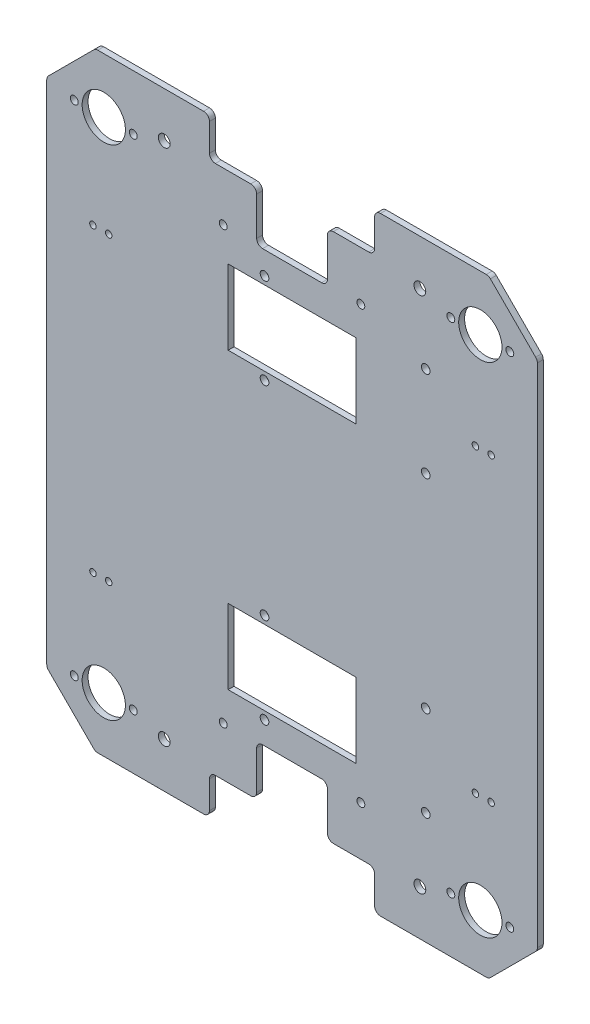
SolidWorks part; units mm, degrees
material "Alliage 1060"
ref_plane "Plan de dessus" through (0, 0, 0) normal (0, 0, 1) x (1, 0, 0)
ref_plane "Plan de droite" through (0, 0, 0) normal (0, 1, 0) x (1, 0, 0)
ref_plane "Plan de face" through (0, 0, 0) normal (1, 0, 0) x (0, 0, -1)
sketch "Esquisse1" plane through (0, 0, 0) normal (0, 0, 1) x (1, 0, 0)
  line L0 (0, 0) -> (-200, 0)
  line L1 (-200, 0) -> (-224.7487, 24.7487)
  line L2 (-224.7487, 24.7487) -> (-224.7487, 284.7487)
  line L3 (-224.7487, 284.7487) -> (-200, 309.4975)
  line L4 (-200, 309.4975) -> (0, 309.4975)
  line L5 (0, 309.4975) -> (24.7487, 284.7487)
  line L6 (24.7487, 284.7487) -> (24.7487, 24.7487)
  line L7 (24.7487, 24.7487) -> (0, 0)
  dimension "D1" = 260
  dimension "D2" = 35
  dimension "D3" = 135
  dimension "D4" = 200
extrude "Base" add sketch "Esquisse1" along normal blind 3
sketch "Esquisse3" plane through (0, 0, 0) normal (0, 0, -1) x (-1, 0, 0)
  line L0 (142, 0) -> (142, 20)
  line L1 (200, 0) -> (0, 0) construction
  line L2 (142, 20) -> (118, 20)
  line L3 (118, 20) -> (118, 45.5)
  line L4 (118, 45.5) -> (82, 45.5)
  line L5 (82, 45.5) -> (82, 20)
  line L6 (82, 20) -> (58, 20)
  line L7 (58, 20) -> (58, 0)
  line L8 (-24.7487, 154.7487) -> (224.7487, 154.7487) construction
  line L9 (-24.7487, 24.7487) -> (-24.7487, 284.7487) construction
  line L10 (224.7487, 284.7487) -> (224.7487, 24.7487) construction
  line L11 (58, 0) -> (142, 0)
  line L12 (58, 309.4975) -> (142, 309.4975)
  line L13 (142, 309.4975) -> (142, 289.4975)
  line L14 (142, 289.4975) -> (118, 289.4975)
  line L15 (118, 289.4975) -> (118, 263.9975)
  line L16 (118, 263.9975) -> (82, 263.9975)
  line L17 (82, 263.9975) -> (82, 289.4975)
  line L18 (82, 289.4975) -> (58, 289.4975)
  line L19 (58, 289.4975) -> (58, 309.4975)
  line L20 (100, 45.5) -> (100, -49954.5) construction
  line L21 (0, 309.4975) -> (200, 309.4975) construction
  line L22 (67.5, 244.4975) -> (132.5, 244.4975)
  line L23 (67.5, 244.4975) -> (67.5, 214.4975)
  line L24 (67.5, 214.4975) -> (132.5, 214.4975)
  line L25 (132.5, 244.4975) -> (132.5, 214.4975)
  line L26 (132.5, 65) -> (132.5, 95)
  line L27 (67.5, 95) -> (132.5, 95)
  line L28 (67.5, 65) -> (132.5, 65)
  line L29 (67.5, 65) -> (67.5, 95)
  circle A0 centre (65, 45) radius 2
  circle A1 centre (135, 45) radius 2
  circle A2 centre (135, 264.4975) radius 2
  circle A3 centre (65, 264.4975) radius 2
  point P4 (100, 45.5)
  point P11 (100, 0)
  point P40 (100, 244.4975)
  point P41 (132.5, 229.4975)
  dimension "D7" = 4
  dimension "D5" = 25
  dimension "D1" = 20
  dimension "D2" = 24
  dimension "D3" = 36
  dimension "D4" = 25.5
  dimension "D6" = 7
  dimension "D8" = 80
  dimension "D9" = 30
  dimension "D10" = 65
extrude "Perçage roues encodeuses" cut sketch "Esquisse3" against normal through all
fillet "Congé1" radius 3 24 edges at (-224.7487, 24.7487, 1.5) (24.7487, 24.7487, 1.5) (0, 0, 1.5) (-142, 20, 1.5) (-118, 45.5, 1.5) (-118, 20, 1.5) (-200, 0, 1.5) (-142, 0, 1.5) (-82, 45.5, 1.5) (-58, 20, 1.5) (-82, 20, 1.5) (-58, 0, 1.5) (24.7487, 284.7487, 1.5) (-142, 289.4975, 1.5) (-118, 263.9975, 1.5) (-224.7487, 284.7487, 1.5) (-200, 309.4975, 1.5) (-142, 309.4975, 1.5) (-118, 289.4975, 1.5) (-82, 263.9975, 1.5) (-58, 289.4975, 1.5) (-82, 289.4975, 1.5) (-58, 309.4975, 1.5) (0, 309.4975, 1.5)
sketch "Esquisse6" plane through (0, 0, 3) normal (0, 0, 1) x (1, 0, 0)
  line L0 (-195.7487, 28) -> (-210.7487, 28) construction
  line L1 (-195.7487, 28) -> (-180.7487, 28) construction
  line L2 (-100, 231.5685) -> (-100, -49768.4315) construction
  line L4 (-67.5, 214.4975) -> (-132.5, 214.4975) construction
  line L5 (-203.2843, 154.7487) -> (49796.7157, 154.7487) construction
  line L6 (-224.7487, 283.5061) -> (-224.7487, 25.9914) construction
  line L15 (-198.7574, 0) -> (-145, 0) construction
  circle A25 centre (-180.7487, 28) radius 2
  circle A26 centre (-210.7487, 28) radius 2
  circle A27 centre (-195.7487, 28) radius 11
  circle A31 centre (-19.2513, 28) radius 2
  circle A32 centre (10.7487, 28) radius 2
  circle A33 centre (-4.2513, 28) radius 11
  circle A34 centre (-4.2513, 281.4975) radius 11
  circle A35 centre (10.7487, 281.4975) radius 2
  circle A36 centre (-19.2513, 281.4975) radius 2
  circle A37 centre (-195.7487, 281.4975) radius 11
  circle A38 centre (-210.7487, 281.4975) radius 2
  circle A39 centre (-180.7487, 281.4975) radius 2
  point P15 (-100, 214.4975)
  point P20 (-224.7487, 154.7487)
  dimension "D2" = 4
  dimension "D3" = 15
  dimension "D4" = 15
  dimension "D5" = 180
  dimension "D9" = 29
  dimension "D13" = 22
  dimension "D15" = 28
extrude "Perçage billes porteuses" cut sketch "Esquisse6" against normal up to next
sketch "Esquisse8" plane through (0, 0, 3) normal (0, 0, 1) x (1, 0, 0)
  line L0 (-100, 263.9975) -> (-100, 95) construction
  line L1 (-85, 263.9975) -> (-115, 263.9975) construction
  line L2 (-132.5, 95) -> (-67.5, 95) construction
  line L3 (-145, 309.4975) -> (-198.7574, 309.4975) construction
  line L4 (-142, 292.4975) -> (-142, 306.4975) construction
  line L5 (-198.7574, 0) -> (-145, 0) construction
  line L6 (-142, 3) -> (-142, 17) construction
  circle A0 centre (-165, 23) radius 3
  circle A1 centre (-165, 286.4975) radius 3
  circle A2 centre (-35, 286.4975) radius 3
  circle A3 centre (-35, 23) radius 3
  dimension "D1" = 23
  dimension "D2" = 23
  dimension "D3" = 6
  dimension "D4" = 23
  dimension "D5" = 23
  dimension "D6" = 6
extrude "Perçage profilés" cut sketch "Esquisse8" against normal up to next
sketch "Esquisse10" plane through (0, 0, 3) normal (0, 0, 1) x (1, 0, 0)
  line L0 (-224.7487, 283.5061) -> (-224.7487, 25.9914) construction
  line L1 (-100, 214.4975) -> (-100, 95) construction
  line L2 (-123.75, 179.6975) -> (-100, 179.6975) construction
  line L3 (-67.5, 214.4975) -> (-132.5, 214.4975) construction
  line L4 (-100, 179.6975) -> (21.8665, 179.6975) construction
  line L5 (-224.7487, 154.7487) -> (24.7487, 154.7487) construction
  line L6 (24.7487, 25.9914) -> (24.7487, 283.5061) construction
  line L7 (-132.5, 95) -> (-67.5, 95) construction
  line L8 (-158.75, 179.6975) -> (-123.75, 179.6975) construction
  line L9 (-132.5, 229.4975) -> (-67.5, 229.4975) construction
  line L10 (-132.5, 214.4975) -> (-132.5, 244.4975) construction
  line L11 (-67.5, 244.4975) -> (-67.5, 214.4975) construction
  line L12 (-100, 129.8) -> (-139.6239, 129.8) construction
  line L13 (-100, 129.8) -> (10.2968, 129.8) construction
  circle A8 centre (-123.75, 179.6975) radius 1.75
  circle A9 centre (-120, 208.4975) radius 1.75
  circle A10 centre (-158.75, 179.6975) radius 1.75
  circle A11 centre (-80, 208.4975) radius 1.75
  circle A18 centre (-80, 101) radius 1.75
  circle A19 centre (-120, 101) radius 1.75
  circle A20 centre (-71.75, 179.6975) radius 1.75
  circle A21 centre (-40.75, 179.6975) radius 1.75
  circle A22 centre (-128.25, 129.8) radius 1.75
  circle A23 centre (-159.25, 129.8) radius 1.75
  circle A24 centre (-76.25, 129.8) radius 1.75
  circle A25 centre (-41.25, 129.8) radius 1.75
  dimension "D1" = 3.5
  dimension "D2" = 23.75
  dimension "D3" = 20
  dimension "D4" = 3.5
  dimension "D5" = 3.5
  dimension "D6" = 35
  dimension "D7" = 21
  dimension "D8" = 28.8
  dimension "D9" = 3.5
  dimension "D10" = 3.5
  dimension "D12" = 31
  dimension "D13" = 28.8
  dimension "D14" = 3.5
  dimension "D15" = 3.5
  dimension "D16" = 3.5
  dimension "D17" = 3.5
  dimension "D18" = 28.25
  dimension "D19" = 31
  dimension "D21" = 35
  dimension "D11" = 28.25
  dimension "D20" = 23.75
sketch "Esquisse15" plane through (0, 0, 0) normal (0, 0, -1) x (-1, 0, 0)
  line L0 (114, 103) -> (32, 103) construction
  line L1 (-24.7487, 154.7487) -> (23.202, 154.7487) construction
  line L2 (-24.7487, 25.9914) -> (-24.7487, 283.5061) construction
  line L3 (100, 95) -> (100, 134.4542) construction
  line L4 (132.5, 95) -> (67.5, 95) construction
  line L5 (0, 80) -> (59.1109, 80) construction
  line L6 (55, 0) -> (1.2426, 0) construction
  circle A0 centre (114, 103) radius 2.2
  circle A1 centre (32, 103) radius 2.2
  circle A2 centre (114, 57) radius 2.2
  circle A3 centre (32, 57) radius 2.2
  circle A4 centre (32, 252.4975) radius 2.2
  circle A5 centre (114, 252.4975) radius 2.2
  circle A6 centre (114, 206.4975) radius 2.2
  circle A7 centre (32, 206.4975) radius 2.2
  dimension "D2" = 4.4
  dimension "D1" = 82
  dimension "D3" = 80
  dimension "D4" = 23
  dimension "D5" = 14
extrude "Perçage bloc moteur" cut sketch "Esquisse15" against normal up to surface (3 mm away) up to face at (-38, 23, 3)
sketch "Esquisse16" plane through (0, 0, 0) normal (0, 0, -1) x (-1, 0, 0)
  line L0 (224.7487, 154.7487) -> (-24.7487, 154.7487) construction
  line L1 (67.5, 61) -> (132.5, 61)
  line L2 (67.5, 61) -> (67.5, 99)
  line L3 (67.5, 99) -> (132.5, 99)
  line L4 (132.5, 61) -> (132.5, 99)
  line L5 (224.7487, 283.5061) -> (224.7487, 25.9914) construction
  line L6 (-24.7487, 25.9914) -> (-24.7487, 283.5061) construction
  line L7 (100, 309.4975) -> (100, 0) construction
  line L8 (100, 0) -> (55, 0) construction
  line L9 (67.5, 210.4975) -> (132.5, 210.4975)
  line L10 (132.5, 248.4975) -> (132.5, 210.4975)
  line L11 (67.5, 248.4975) -> (132.5, 248.4975)
  line L12 (67.5, 248.4975) -> (67.5, 210.4975)
  line L13 (198.7574, 0) -> (145, 0) construction
  point P10 (132.5, 80)
  point P13 (100, 154.7487)
  point P16 (100, 61)
  dimension "D1" = 80
  dimension "D2" = 38
  dimension "D3" = 65
extrude "Enlèv. mat.-Extru.1" cut sketch "Esquisse16" against normal through all
sketch "Esquisse14" plane through (0, 309.4975, 0) normal (0, 1, 0) x (1, 0, 0)
  line L0 (-100, -3) -> (-100, 0) construction
  line L1 (-85, -3) -> (-115, -3) construction
  line L2 (-85, 0) -> (-115, 0) construction
sketch "Esquisse18" plane through (0, 0, 0) normal (0, 0, -1) x (-1, 0, 0)
  line L0 (224.7487, 154.7487) -> (-24.7487, 154.7487) construction
  line L1 (224.7487, 283.5061) -> (224.7487, 25.9914) construction
  line L2 (-24.7487, 25.9914) -> (-24.7487, 283.5061) construction
  line L3 (100, 0) -> (100, 309.4975) construction
  line L4 (197.2487, 231.2487) -> (197.2487, 78.2487) construction
  line L5 (201.2487, 78.2487) -> (193.2487, 78.2487)
  circle A0 centre (201.2487, 78.2487) radius 1.65
  circle A1 centre (193.2487, 78.2487) radius 1.65
  circle A2 centre (193.2487, 231.2487) radius 1.65
  circle A3 centre (201.2487, 231.2487) radius 1.65
  circle A4 centre (-1.2487, 231.2487) radius 1.65
  circle A5 centre (6.7513, 231.2487) radius 1.65
  circle A6 centre (-1.2487, 78.2487) radius 1.65
  circle A7 centre (6.7513, 78.2487) radius 1.65
  point P8 (100, 154.7487)
  point P12 (197.2487, 154.7487)
  point P15 (197.2487, 78.2487)
  dimension "D2" = 3.3
  dimension "D1" = 153
  dimension "D3" = 8
  dimension "D4" = 27.5
extrude "Enlèv. mat.-Extru.2" cut sketch "Esquisse18" against normal through all contours A6 | A7 | A4 | A5 | A2 | A3 | A1 | A0
